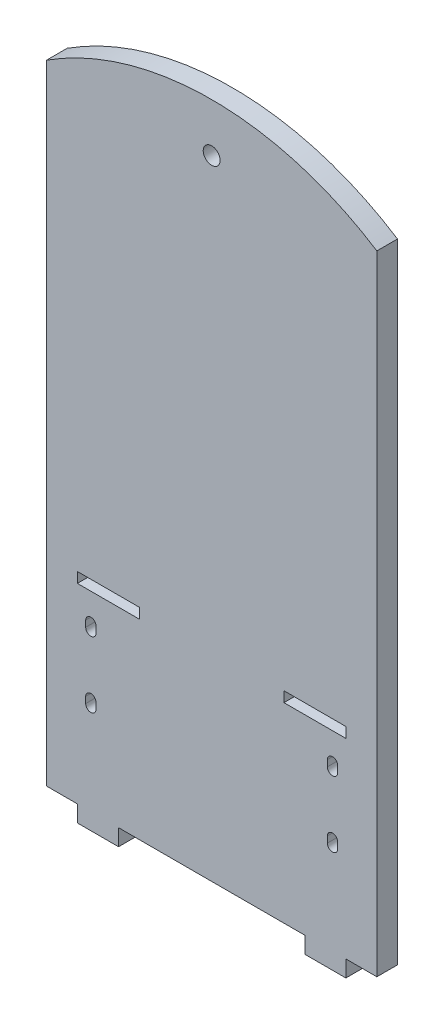
SolidWorks part; units mm, degrees
ref_plane "前基準面" through (0, 0, 0) normal (0, 0, 1) x (1, 0, 0)
ref_plane "上基準面" through (0, 0, 0) normal (0, 1, 0) x (1, 0, 0)
ref_plane "右基準面" through (0, 0, 0) normal (1, 0, 0) x (0, 0, -1)
sketch "草圖1" plane through (0, 0, 0) normal (0, 0, 1) x (1, 0, 0)
  line L0 (-80, 0) -> (-65, 0)
  line L1 (-80, 0) -> (-80, 304.5)
  line L2 (80, 0) -> (80, 304.5)
  line L3 (0, 299.9843) -> (0, -20.7711) construction
  line L5 (-65, 0) -> (-65, -8)
  line L6 (-65, -8) -> (-45.1, -8)
  line L7 (-45.1, 0) -> (-45.1, -8)
  line L12 (65, -8) -> (45.1, -8)
  line L13 (45.1, 0) -> (45.1, -8)
  line L15 (65, 0) -> (65, -8)
  line L16 (-45.1, 0) -> (45.1, 0)
  line L17 (65, 0) -> (80, 0)
  line L18 (-21.8, 304.5) -> (-15, 33.5) construction
  line L19 (28.5, 5) -> (-28.5, 5) construction
  line L20 (28.5, 5) -> (28.5, 62) construction
  line L21 (28.5, 62) -> (-28.5, 62) construction
  line L22 (-28.5, 5) -> (-28.5, 62) construction
  line L23 (21.8, 304.5) -> (15, 33.5) construction
  line L24 (-58.525, 76.1) -> (-58.525, 79.1) construction
  line L25 (-61.025, 76.1) -> (-61.025, 79.1)
  line L26 (-56.025, 76.1) -> (-56.025, 79.1)
  line L27 (-58.525, 44.1) -> (-58.525, 47.1) construction
  line L28 (-61.025, 44.1) -> (-61.025, 47.1)
  line L29 (-56.025, 44.1) -> (-56.025, 47.1)
  line L30 (-67.625, 89.2) -> (-67.625, 34) construction
  line L31 (-67.625, 89.2) -> (-49.425, 89.2) construction
  line L32 (-49.425, 89.2) -> (-49.425, 34) construction
  line L33 (-67.625, 34) -> (-49.425, 34) construction
  line L34 (-49.425, 61.6) -> (-67.625, 61.6) construction
  line L35 (-58.525, 89.2) -> (-58.525, 34) construction
  line L36 (58.525, 44.1) -> (58.525, 47.1) construction
  line L37 (61.025, 44.1) -> (61.025, 47.1)
  line L38 (56.025, 44.1) -> (56.025, 47.1)
  line L39 (58.525, 76.1) -> (58.525, 79.1) construction
  line L40 (61.025, 76.1) -> (61.025, 79.1)
  line L41 (56.025, 76.1) -> (56.025, 79.1)
  line L42 (76.4706, 328) -> (-76.4706, 328) construction
  arc A0 (-80, 304.5) -> (80, 304.5) centre (0, 304.5) cw construction
  circle A1 centre (0, 304.5) radius 4.1
  circle A2 centre (0, 33.5) radius 4 construction
  circle A3 centre (0, 33.5) radius 15 construction
  circle A4 centre (0, 304.5) radius 21.8 construction
  arc A5 (-61.025, 76.1) -> (-56.025, 76.1) centre (-58.525, 76.1) ccw
  arc A6 (-56.025, 79.1) -> (-61.025, 79.1) centre (-58.525, 79.1) ccw
  arc A7 (-61.025, 44.1) -> (-56.025, 44.1) centre (-58.525, 44.1) ccw
  arc A8 (-56.025, 47.1) -> (-61.025, 47.1) centre (-58.525, 47.1) ccw
  arc A9 (61.025, 44.1) -> (56.025, 44.1) centre (58.525, 44.1) cw
  arc A10 (56.025, 47.1) -> (61.025, 47.1) centre (58.525, 47.1) cw
  arc A11 (61.025, 76.1) -> (56.025, 76.1) centre (58.525, 76.1) cw
  arc A12 (56.025, 79.1) -> (61.025, 79.1) centre (58.525, 79.1) cw
  arc A13 (-80, 304.5) -> (80, 304.5) centre (0, 180.0798) cw
  point P17 (0, 62)
  point P25 (-28.5, 33.5)
  point P31 (-58.525, 77.6)
  point P39 (-58.525, 45.6)
  point P45 (-58.525, 49.6)
  point P46 (-58.525, 73.6)
  point P47 (-58.525, 41.6)
  point P48 (-58.525, 81.6)
  point P49 (-58.525, 61.6)
  point P63 (58.525, 45.6)
  point P70 (58.525, 77.6)
  point P78 (0, 384.5)
  dimension "D2" = 8.2
  dimension "D8" = 8
  dimension "D9" = 43.6
  dimension "D11" = 30
  dimension "D22" = 328
  dimension "D1" = 160
  dimension "D3" = 8
  dimension "D4" = 19.9
  dimension "D5" = 15
  dimension "D6" = 57
  dimension "D7" = 57
  dimension "D10" = 271
  dimension "D12" = 24
  dimension "D13" = 40
  dimension "D14" = 5
  dimension "D15" = 7.6
  dimension "D16" = 18.2
  dimension "D17" = 34
  dimension "D18" = 5.25
  dimension "D19" = 392.5
  dimension "D20" = 5
  dimension "D21" = 55.2
extrude "填料-伸長1" add sketch "草圖1" against normal blind 10
sketch "草圖2" plane through (0, 0, 0) normal (0, 0, 1) x (1, 0, 0)
  line L0 (20.9897, 303.8413) -> (12.4938, 33.1079) construction
  line L1 (-20.9897, 303.8413) -> (-12.4938, 33.1079) construction
  line L2 (85.3199, 95) -> (-141.7674, 95) construction
  line L3 (28.5, 62) -> (-28.5, 62) construction
  line L4 (28.5, 62) -> (28.5, 5) construction
  line L5 (28.5, 5) -> (-28.5, 5) construction
  line L6 (-28.5, 62) -> (-28.5, 5) construction
  line L7 (0, 5) -> (0, 62) construction
  line L8 (28.5, 33.5) -> (-28.5, 33.5) construction
  line L9 (-45.1, 0) -> (45.1, 0) construction
  line L10 (0, 0) -> (0, 407.6307) construction
  line L11 (-107.05, 139.5) -> (7, 139.5) construction
  line L12 (35, 97.5) -> (65.05, 97.5)
  line L13 (35, 97.5) -> (35, 92.5)
  line L14 (35, 92.5) -> (65.05, 92.5)
  line L15 (65.05, 97.5) -> (65.05, 92.5)
  line L16 (50.025, 92.5) -> (50.025, 97.5) construction
  line L17 (35, 95) -> (65.05, 95) construction
  line L18 (-65.05, 97.5) -> (-35, 97.5)
  line L19 (-65.05, 97.5) -> (-65.05, 92.5)
  line L20 (-65.05, 92.5) -> (-35, 92.5)
  line L21 (-35, 97.5) -> (-35, 92.5)
  line L22 (-50.025, 92.5) -> (-50.025, 97.5) construction
  line L23 (-65.05, 95) -> (-35, 95) construction
  line L27 (-107.05, 139.5) -> (-107.05, 50.5) construction
  line L28 (-107.05, 50.5) -> (7, 50.5) construction
  line L29 (7, 139.5) -> (7, 50.5) construction
  circle A0 centre (0, 304.5) radius 4.1 construction
  circle A1 centre (0, 304.5) radius 4.1 construction
  circle A2 centre (0, 33.5) radius 4 construction
  circle A3 centre (0, 33.5) radius 4 construction
  circle A4 centre (0, 304.5) radius 21 construction
  circle A5 centre (0, 33.5) radius 12.5 construction
  point P24 (50.025, 95)
  point P28 (-50.025, 95)
  point P35 (14.4361, 95)
  point P37 (-14.4361, 95)
  dimension "D1" = 25
  dimension "D2" = 42
  dimension "D3" = 57
  dimension "D4" = 57
  dimension "D5" = 95
  dimension "D6" = 5
  dimension "D7" = 30.05
  dimension "D8" = 70
  dimension "D9" = 28.8721
  dimension "D10" = 42
  dimension "D11" = 165
extrude "除料-伸長1" cut sketch "草圖2" against normal through all
